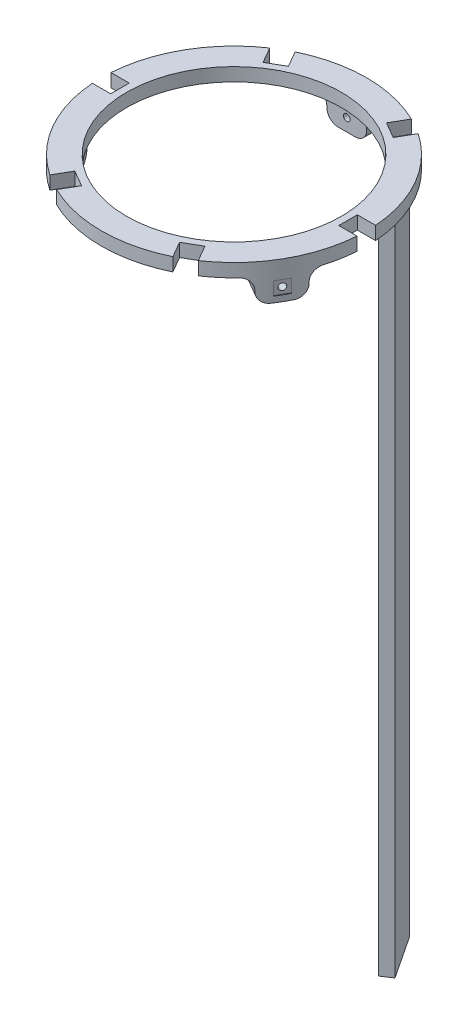
SolidWorks part; units mm, degrees
ref_plane "Спереди" through (0, 0, 0) normal (0, 0, 1) x (1, 0, 0)
ref_plane "Сверху" through (0, 0, 0) normal (0, 1, 0) x (1, 0, 0)
ref_plane "Справа" through (0, 0, 0) normal (1, 0, 0) x (0, 0, -1)
sketch "Эскиз1" plane through (0, 0, 0) normal (0, 1, 0) x (1, 0, 0)
  circle A0 centre (0, 0) radius 100
  dimension "D1" = 200
extrude "Бобышка-Вытянуть1" add sketch "Эскиз1" along normal blind 10
sketch "Эскиз2" plane through (0, 10, 0) normal (0, 1, 0) x (1, 0, 0)
  line L0 (-93, 0) -> (0, 0) construction
  line L1 (-100, 7) -> (-86, 7)
  line L2 (-100, 7) -> (-100, -7)
  line L3 (-100, -7) -> (-86, -7)
  line L4 (-86, 7) -> (-86, -7)
  line L5 (-100, 7) -> (-86, -7) construction
  line L6 (-100, -7) -> (-86, 7) construction
  circle A0 centre (0, 0) radius 100 construction
  point P0 (-93, 0)
  dimension "D1" = 14
  dimension "D2" = 14
extrude "Вырез-Вытянуть1" cut sketch "Эскиз2" against normal through all
pattern_circular "Круговой массив1" count 6 over 360 about axis through (0, 10, 0) along (0, 1, 0) of "Вырез-Вытянуть1"
sketch "Эскиз3" plane through (0, 10, 0) normal (0, 1, 0) x (1, 0, 0)
  line L1 (-86, -7) -> (-86, 7) construction
  circle A0 centre (0, 0) radius 81
  point P5 (-81, 0)
  dimension "D1" = 5
extrude "Вырез-Вытянуть2" cut sketch "Эскиз3" against normal through all
ref_plane "Плоскость1" through (0, 0, -100) normal (0, 0, -1) x (-1, 0, 0)
sketch "Эскиз6" plane through (0, 0, -100) normal (0, 0, -1) x (-1, 0, 0)
  line L0 (-43.8152, 0) -> (43.8152, 0) construction
  line L1 (-15, -17.9681) -> (15, -17.9681)
  line L2 (-15, -17.9681) -> (-15, 0)
  line L3 (-15, 0) -> (15, 0)
  line L4 (15, -17.9681) -> (15, 0)
  line L5 (-15, -17.9681) -> (15, 0) construction
  line L6 (-15, 0) -> (15, -17.9681) construction
  line L7 (0, -8.984) -> (0, 0) construction
  point P0 (0, -8.984)
  dimension "D1" = 30
extrude "Бобышка-Вытянуть2" add sketch "Эскиз6" against normal blind 15
sketch "Эскиз7" plane through (0, 10, 0) normal (0, 1, 0) x (1, 0, 0)
  circle A0 centre (0, 0) radius 100
  arc A1 (43.8152, 89.8901) -> (-43.8152, 89.8901) centre (0, 0) ccw construction
  circle A2 centre (0, 0) radius 105
  dimension "D1" = 5
extrude "Вырез-Вытянуть3" cut sketch "Эскиз7" against normal through all
sketch "Эскиз8" plane through (0, 0, -100) normal (0, 0, -1) x (-1, 0, 0)
  line L0 (0, -8.5) -> (0, 0) construction
  circle A0 centre (0, -8.5) radius 2.5
  dimension "D2" = 5
  dimension "D1" = 8.5
extrude "Вырез-Вытянуть4" cut sketch "Эскиз8" against normal up to next
fillet "Скругление1" radius 8.5 4 edges at (-15, 0, -91.9343) (15, 0, -91.9343) (-15, -17.9681, -91.9343) (15, -17.9681, -91.9343)
sketch "Эскиз9" plane through (0, 0, -100) normal (0, 0, -1) x (-1, 0, 0)
  line L1 (-5, -3.5) -> (5, -3.5)
  line L2 (-5, -3.5) -> (-5, -13.5)
  line L3 (-5, -13.5) -> (5, -13.5)
  line L4 (5, -3.5) -> (5, -13.5)
  line L5 (-5, -3.5) -> (5, -13.5) construction
  line L6 (-5, -13.5) -> (5, -3.5) construction
  point P0 (0, -8.5)
  dimension "D1" = 10
  dimension "D2" = 10
extrude "Вырез-Вытянуть5" cut sketch "Эскиз9" against normal blind 0.5
pattern_circular "Круговой массив3" count 3 over 360 about axis through (0, 0, 0) along (0, 1, 0) of "Бобышка-Вытянуть2", "Вырез-Вытянуть3", "Вырез-Вытянуть4", "Скругление1", "Вырез-Вытянуть5"
sketch "Эскиз10" plane through (0, 0, 0) normal (0, -1, 0) x (1, 0, 0)
  line L0 (67.0955, -65.2982) -> (88.5621, -32.8102)
  line L1 (88.5621, -32.8102) -> (81.0551, -27.8499)
  line L2 (81.0551, -27.8499) -> (59.5884, -60.3378)
  line L3 (59.5884, -60.3378) -> (67.0955, -65.2982)
extrude "Бобышка-Вытянуть3" add sketch "Эскиз10" along normal blind 500
